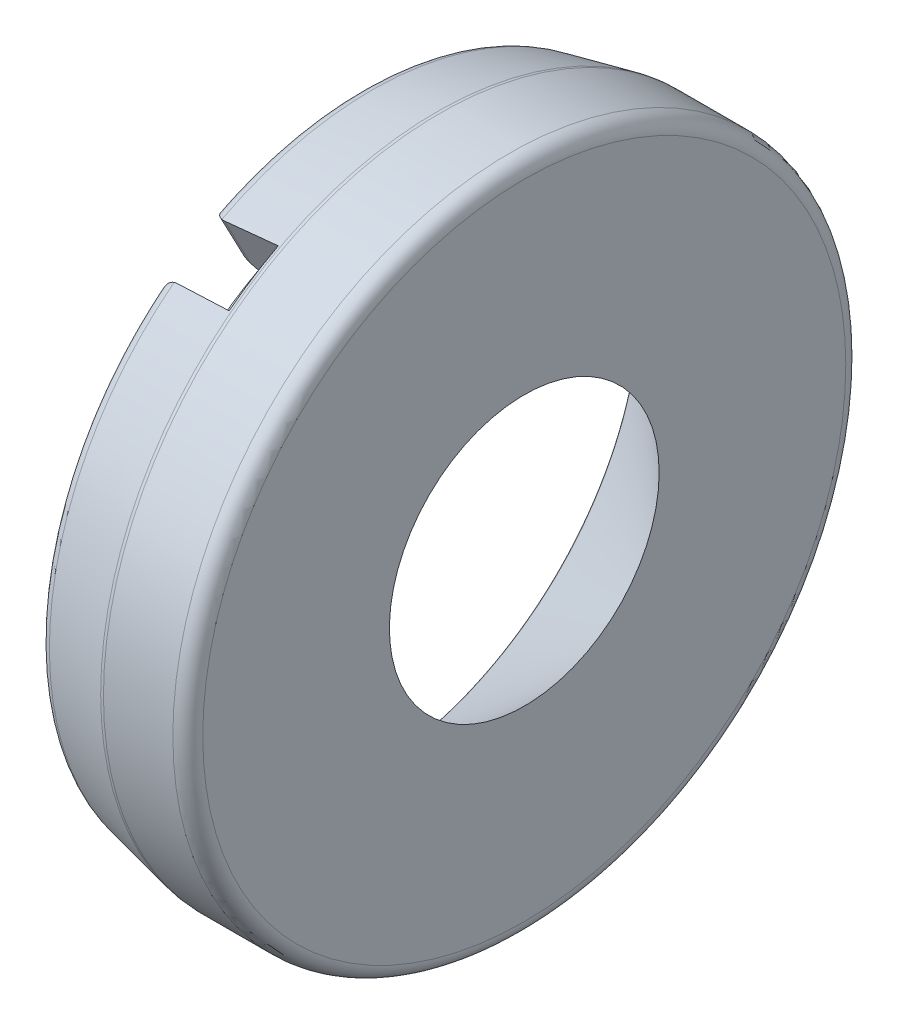
SolidWorks part; units mm, degrees
material "PC 高粘度"
ref_plane "前视基准面" through (0, 0, 0) normal (0, 0, 1) x (1, 0, 0)
ref_plane "上视基准面" through (0, 0, 0) normal (0, 1, 0) x (1, 0, 0)
ref_plane "右视基准面" through (0, 0, 0) normal (1, 0, 0) x (0, 0, -1)
sketch "草图1" plane through (0, 0, 0) normal (0, 0, 1) x (1, 0, 0)
  line L1 (-14.5696, 0) -> (-16.7696, 1.937)
  line L2 (-16.7696, 1.937) -> (-16.7696, 2.4717)
  line L4 (-14.5696, 2.4717) -> (-14.5696, 0)
  line L5 (-16.7696, 2.4717) -> (-15.7191, 2.6961)
  line L6 (-15.7191, 2.6961) -> (-14.5696, 2.6961)
  line L7 (-14.5696, 2.6961) -> (-14.5696, 2.4717)
  line L8 (-14.5696, 2.6961) -> (-14.5696, 0)
  line L9 (-14.5696, -1.8039) -> (-17.5233, -1.8039)
revolve "旋转1" add sketch "草图1" angle 360 about L9 region at (-15.4335, 1.7136, 0)
sketch "草图6" plane through (-16.7696, 0, 0) normal (-1, 0, 0) x (0, 0, 1)
  line L0 (1.6294, 1.2937) -> (2.0949, 2.1787)
  line L1 (2.1425, 0.9637) -> (2.7547, 1.7544)
  arc A0 (2.7547, 1.7544) -> (2.0949, 2.1787) centre (0, -1.8039) ccw
  arc A1 (2.1425, 0.9637) -> (1.6294, 1.2937) centre (0, -1.8039) ccw
  dimension "D1" = 10
extrude "切除-拉伸1" cut sketch "草图6" against normal blind 1
ref_axis "基准轴1" through (-16.7696, -1.8039, 0) along (1, 0, 0)
pattern_circular "阵列(圆周)1" count 3 over 360 about axis through (-16.7696, -1.8039, 0) along (1, 0, 0) of "切除-拉伸1"
fillet "圆角1" radius 0.2 14 edges at (-15.7191, -1.8039, -4.5) (-14.5696, -1.8039, -4.5) (-16.7696, 1.3656, 2.4537) (-16.7696, -2.0087, 4.2707) (-16.7696, -5.1937, 2.1392) (-16.7696, -1.9831, 3.7366) (-16.7696, 1.7435, 1.866) (-16.7696, 1.5217, -1.7131) (-16.7696, -1.2637, -3.9717) (-16.7696, 1.997, -1.958) (-16.7696, -5.5136, 1.518) (-16.7696, -5.4001, -2.3127) (-16.7696, -1.9616, -4.0052) (-16.7696, -4.9504, -2.0235)
